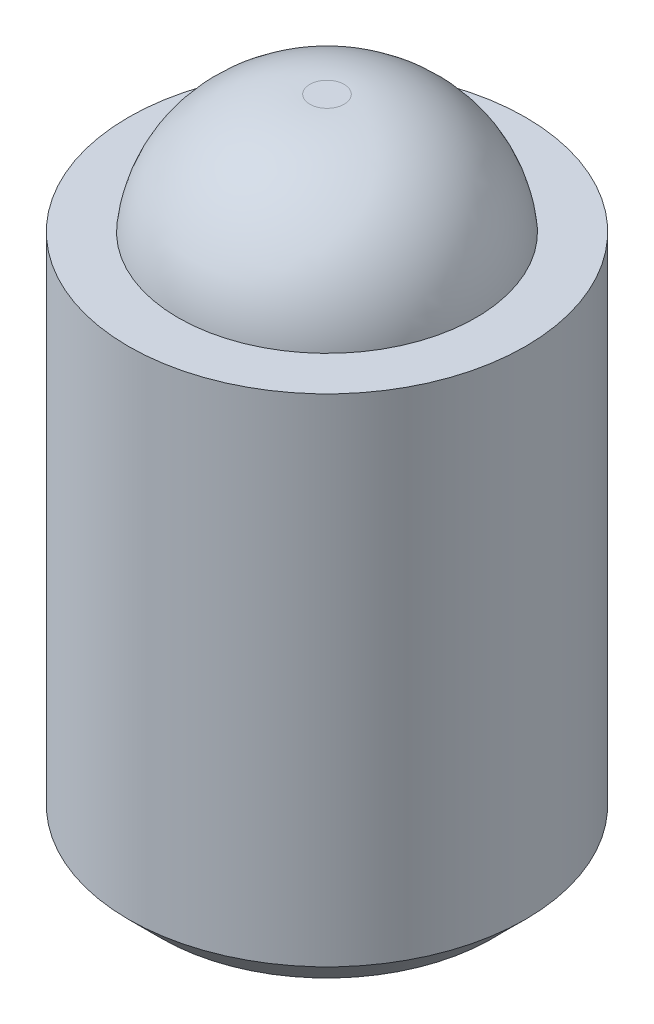
SolidWorks part; units mm, degrees
ref_plane "前视基准面" through (0, 0, 0) normal (0, 0, 1) x (1, 0, 0)
ref_plane "上视基准面" through (0, 0, 0) normal (0, 1, 0) x (1, 0, 0)
ref_plane "右视基准面" through (0, 0, 0) normal (1, 0, 0) x (0, 0, -1)
sketch "草图1" plane through (0, 0, 0) normal (0, 1, 0) x (1, 0, 0)
  circle A0 centre (0, 0) radius 3
  dimension "D1" = 6
extrude "凸台-拉伸1" add sketch "草图1" along normal blind 8
sketch "草图2" plane through (0, 8, 0) normal (0, 1, 0) x (1, 0, 0)
  circle A0 centre (0, 0) radius 2.25
  dimension "D1" = 4.5
extrude "凸台-拉伸2" add sketch "草图2" along normal blind 1.8
fillet "圆角2" radius 2 1 edges at (0, 9.8, 2.25)
chamfer "倒角1" distance 0.5 angle 45 1 edges at (0, 0, 3)
sketch "草图3" plane through (0, 0, 0) normal (0, -1, 0) x (1, 0, 0)
  line L1 (0, 1.8088) -> (-1.5664, 0.9044)
  line L2 (-1.5664, 0.9044) -> (-1.5664, -0.9044)
  line L3 (-1.5664, -0.9044) -> (0, -1.8088)
  line L4 (0, -1.8088) -> (1.5664, -0.9044)
  line L5 (1.5664, -0.9044) -> (1.5664, 0.9044)
  line L6 (1.5664, 0.9044) -> (0, 1.8088)
  circle A0 centre (0, 0) radius 1.5664 construction
extrude "切除-拉伸1" cut sketch "草图3" against normal blind 1.8
